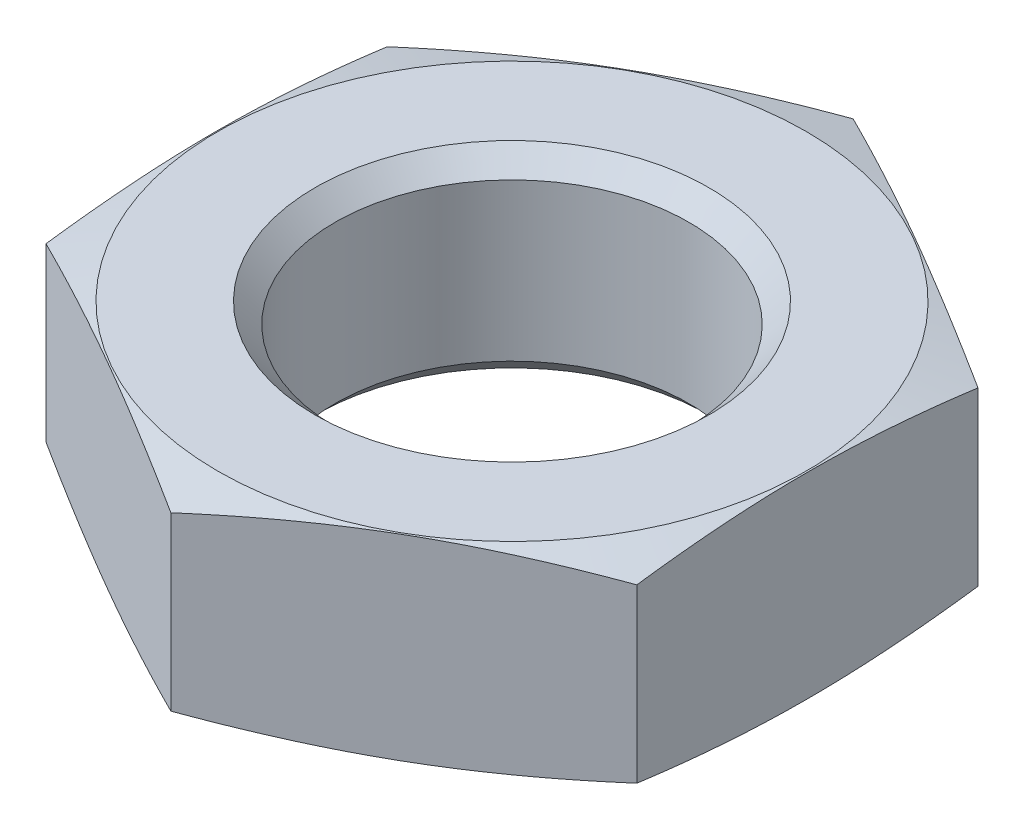
SolidWorks part; units mm, degrees
ref_plane "Front Plane" through (0, 0, 0) normal (0, 0, 1) x (1, 0, 0)
ref_plane "Top Plane" through (0, 0, 0) normal (0, 1, 0) x (1, 0, 0)
ref_plane "Right Plane" through (0, 0, 0) normal (1, 0, 0) x (0, 0, -1)
ref_plane "Plane1" through (0, 0, 0) normal (0, 0, 1) x (1, 0, 0)
sketch "Sketch1" plane through (0, 0, 0) normal (0, 0, 1) x (1, 0, 0)
  line L0 (0, 0) -> (11.95, 0)
  line L1 (11.95, 0) -> (26.8782, -4)
  line L2 (26.8782, -4) -> (11.95, -8)
  line L3 (11.95, -8) -> (0, -8)
  line L4 (0, -8) -> (0, 0)
  line L5 (0, -8) -> (0, 0) construction
revolve "Revolve1" add sketch "Sketch1" angle 360 about L5
ref_plane "Plane2" through (0, 0, 0) normal (0, 1, 0) x (1, 0, 0)
sketch "Sketch2" plane through (0, 0, 0) normal (0, 1, 0) x (1, 0, 0)
  line L0 (-48, 48) -> (-48, -48)
  line L1 (-48, -48) -> (48, -48)
  line L2 (48, -48) -> (48, 48)
  line L3 (48, 48) -> (-48, 48)
  line L4 (-12, -6.9282) -> (0, -13.8564)
  line L5 (0, -13.8564) -> (12, -6.9282)
  line L6 (12, -6.9282) -> (12, 6.9282)
  line L7 (12, 6.9282) -> (0, 13.8564)
  line L8 (0, 13.8564) -> (-12, 6.9282)
  line L9 (-12, 6.9282) -> (-12, -6.9282)
extrude "Cut-Extrude1" cut sketch "Sketch2" against normal blind 9 and the other way blind 9
ref_plane "Plane3" through (0, 0, 0) normal (0, 0, 1) x (1, 0, 0)
sketch "Sketch3" plane through (0, 0, 0) normal (0, 0, 1) x (1, 0, 0)
  line L0 (0, 0) -> (8, 0)
  line L1 (8, 0) -> (7.188, -0.812)
  line L2 (7.188, -0.812) -> (7.188, -7.188)
  line L3 (7.188, -7.188) -> (8, -8)
  line L4 (8, -8) -> (0, -8)
  line L5 (0, -8) -> (0, 0)
  line L6 (0, -8) -> (0, 0) construction
revolve "Cut-Revolve1" cut sketch "Sketch3" angle 360 about L6 reverse direction yes
cosmetic thread "Cosmetic Thread1" parameters "D1"=8, "D2"=16
